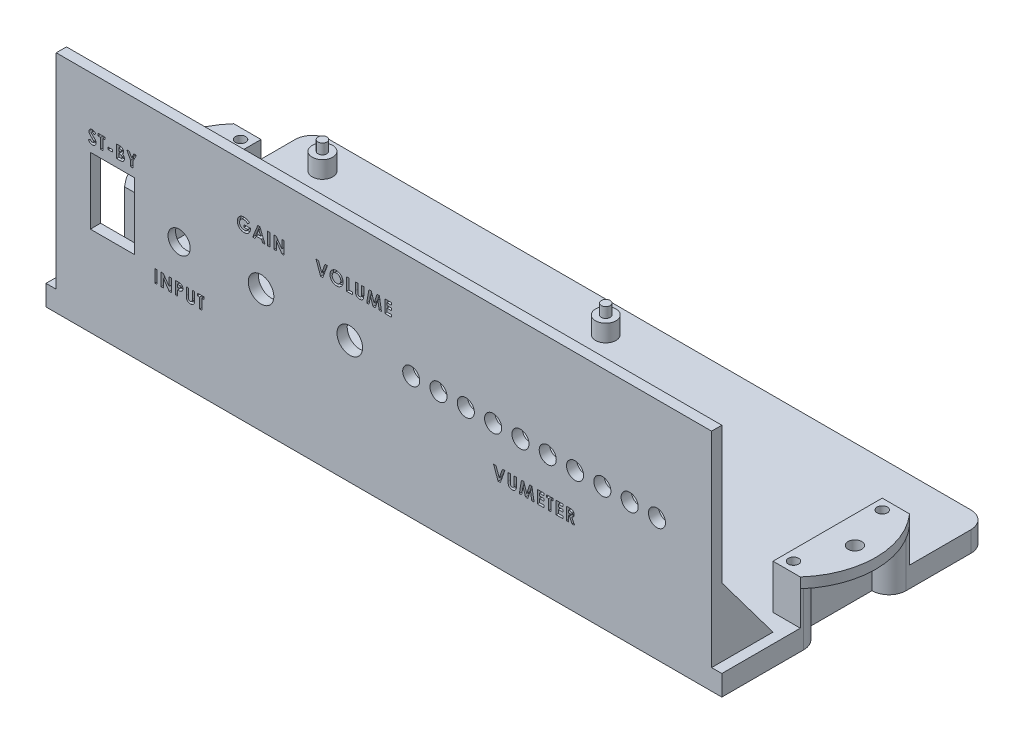
SolidWorks part; units mm, degrees
ref_plane "Alzado" through (0, 0, 0) normal (0, 0, 1) x (1, 0, 0)
ref_plane "Planta" through (0, 0, 0) normal (0, 1, 0) x (1, 0, 0)
ref_plane "Vista lateral" through (0, 0, 0) normal (1, 0, 0) x (0, 0, -1)
sketch "Croquis1" plane through (0, 0, 0) normal (0, 1, 0) x (1, 0, 0)
  line L0 (0, 39) -> (0, -39) construction
  line L1 (-99, 39) -> (99, 39)
  line L3 (-99, -39) -> (99, -39)
  line L10 (99, 39) -> (99, 10)
  line L11 (99, 10) -> (94, 10)
  line L12 (94, 10) -> (94, -10)
  line L13 (94, -10) -> (99, -10)
  line L14 (99, -10) -> (99, -39)
  line L15 (-99, 39) -> (-99, 10)
  line L16 (-99, 10) -> (-94, 10)
  line L17 (-94, 10) -> (-94, -10)
  line L18 (-94, -10) -> (-99, -10)
  line L19 (-99, -10) -> (-99, -39)
  line L20 (-94, 0) -> (4, 0) construction
  circle A0 centre (83, 5) radius 2
  circle A1 centre (6, 5) radius 2
  point P7 (0, 0)
  point P14 (-94, 0)
  point P16 (94, 0)
  dimension "D10" = 4
  dimension "D11" = 4
  dimension "D1" = 78
  dimension "D2" = 198
  dimension "D4" = 20
  dimension "D6" = 39
  dimension "D7" = 5
  dimension "D3" = 20
  dimension "D5" = 5
  dimension "D8" = 39
  dimension "D9" = 5
  dimension "D12" = 77
  dimension "14" = 11
  dimension "D14" = 44
extrude "Saliente-Extruir1" add sketch "Croquis1" along normal blind 6
sketch "Croquis18" plane through (0, 0, 0) normal (0, -1, 0) x (1, 0, 0)
  circle A0 centre (83, -5) radius 4
  circle A1 centre (6, -5) radius 4
  dimension "D1" = 8
  dimension "D2" = 8
extrude "Cortar-Extruir4" cut sketch "Croquis18" against normal blind 3
sketch "Croquis3" plane through (0, 6, 0) normal (0, 1, 0) x (1, 0, 0)
  line L17 (-99, 16) -> (-91, 16)
  line L18 (-99, 39) -> (-99, 10) construction
  line L19 (-91, 16) -> (-91, -16)
  line L20 (-91, -16) -> (-99, -16)
  line L21 (-99, -10) -> (-99, -39) construction
  line L22 (-99, -16) -> (-99, -10)
  line L23 (-99, -10) -> (-94, -10)
  line L24 (-94, -10) -> (-94, 10)
  line L25 (-94, 10) -> (-99, 10)
  line L26 (-99, 10) -> (-99, 16)
  line L27 (91, -16) -> (99, -16)
  line L28 (99, -39) -> (99, -10) construction
  line L29 (99, -16) -> (99, -10)
  line L30 (99, -10) -> (94, -10)
  line L31 (94, -10) -> (94, 10)
  line L32 (94, 10) -> (99, 10)
  line L33 (99, 10) -> (99, 16)
  line L34 (99, 10) -> (99, 39) construction
  line L35 (99, 16) -> (91, 16)
  line L36 (91, 16) -> (91, -16)
  point P26 (95, -16)
  line M5 (-99, 39) -> (-99, 10)
  line M13 (99, -39) -> (99, -10)
  line M14 (99, -10) -> (94, -10)
  line M16 (-99, 10) -> (-94, 10)
  line M17 (-94, 10) -> (-94, -10)
  line M18 (-94, -10) -> (-99, -10)
  line M19 (-99, -10) -> (-99, -39)
  line M20 (94, -10) -> (94, 10)
  line M21 (94, 10) -> (99, 10)
  line M22 (99, 10) -> (99, 39)
  dimension "D1" = 6
  dimension "D3" = 3
  dimension "D4" = 3
  dimension "D7" = 6
  dimension "D2" = 6
extrude "Saliente-Extruir2" add sketch "Croquis3" along normal blind 10 contours L20 L19 L17 M5 M16 M17 M18 M19 | L35 L36 L27 M13 M14 M20 M21 M22 region at (-95, 6, -15.6702) region at (91.3298, 6, 0)
sketch "Croquis5" plane through (0, 6, 0) normal (0, 1, 0) x (1, 0, 0)
  line L0 (-99, -39) -> (99, -39) construction
  line L1 (-96, -36) -> (96, -36)
  line L2 (-96, -36) -> (-96, -39)
  line L3 (-96, -39) -> (96, -39)
  line L4 (96, -36) -> (96, -39)
  point P4 (0, -39)
  point P7 (0, -39)
  dimension "D1" = 192
  dimension "D2" = 3
extrude "Saliente-Extruir3" add sketch "Croquis5" along normal blind 60
sketch "Croquis6" plane through (0, 16, 0) normal (0, 1, 0) x (1, 0, 0)
  line L0 (-99, -16) -> (-91, -16)
  line L1 (-91, -16) -> (-91, 16)
  line L2 (-91, 16) -> (-99, 16)
  line L3 (99, -16) -> (91, -16)
  line L4 (91, -16) -> (91, 16)
  line L5 (91, 16) -> (99, 16)
  arc A0 (-99, -16) -> (-99, 16) centre (-81.1115, 0) cw
  arc A1 (99, -16) -> (99, 16) centre (81.1115, 0) ccw
  dimension "D1" = 24
  dimension "D2" = 24
extrude "Saliente-Extruir4" add sketch "Croquis6" along normal blind 3
sketch "Croquis8" plane through (96, 0, 0) normal (1, 0, 0) x (0, 0, -1)
  line L0 (-36, 26) -> (-21, 6)
  line L1 (-36, 66) -> (-36, 6) construction
  line L2 (7, 6) -> (3, 6) construction
  dimension "D1" = 20
  dimension "D2" = 15
rib "Nervio1" sketch "Croquis8" sketch "Croquis8" thickness 3 extrusion direction parallel to sketch draft on no parameters "D1"=3
sketch "Croquis12" plane through (0, 6, 0) normal (0, 1, 0) x (1, 0, 0)
  line L0 (0, -39) -> (0, 39) construction
  line L1 (-96, -39) -> (96, -39) construction
  line L2 (99, 39) -> (-99, 39) construction
ref_plane "Plano1" through (0, 0, 0) normal (1, 0, 0) x (0, 0, -1)
mirror "Simetría1" about plane through (0, 0, 0) normal (1, 0, 0) of "Nervio1"
sketch "Croquis13" plane through (0, 6, 0) normal (0, 1, 0) x (1, 0, 0)
  line L0 (-99, 39) -> (-99, 16) construction
  line L1 (-87, -28) -> (-87, 30) construction
  line L4 (99, 39) -> (-99, 39) construction
  circle A0 centre (-87, -28) radius 3
  circle A1 centre (-87, 30) radius 3
  circle A2 centre (-4, 30) radius 3
  circle A3 centre (-4, -28) radius 3
  dimension "D7" = 6
  dimension "D6" = 6
  dimension "D3" = 6
  dimension "D4" = 6
  dimension "D1" = 58
  dimension "D2" = 12
  dimension "D5" = 83
  dimension "D8" = 9
extrude "Saliente-Extruir5" add sketch "Croquis13" along normal blind 5
sketch "Croquis14" plane through (0, 11, 0) normal (0, 1, 0) x (1, 0, 0)
  circle A0 centre (-87, 30) radius 1.3
  circle A1 centre (-87, -28) radius 1.3
  circle A2 centre (-87, -28) radius 3 construction
  circle A3 centre (-87, 30) radius 3 construction
  circle A4 centre (-4, 30) radius 1.3
  circle A5 centre (-4, -28) radius 1.3
  dimension "D1" = 2.6
  dimension "D2" = 2.6
  dimension "D3" = 2.6
  dimension "D4" = 2.6
extrude "Saliente-Extruir6" add sketch "Croquis14" along normal blind 3
sketch "Croquis15" plane through (0, 19, 0) normal (0, 1, 0) x (1, 0, 0)
  line L0 (-91, -16) -> (-91, 16) construction
  line L1 (91, 16) -> (91, -16) construction
  circle A0 centre (-99, 0) radius 2
  circle A1 centre (99, 0) radius 2
  point P7 (-91, 0)
  point P11 (91, 0)
  dimension "D1" = 4
  dimension "D3" = 4
  dimension "D2" = 8
  dimension "D4" = 8
extrude "Cortar-Extruir1" cut sketch "Croquis15" against normal up to surface (3 mm away) up to face at (98.3519, 16, 0)
fillet "Redondeo1" radius 5 6 edges at (-99, 8, 10) (-99, 8, -10) (-99, 3, -39) (99, 3, -39) (99, 8, 10) (99, 8, -10)
sketch "Croquis16" plane through (0, 19, 0) normal (0, 1, 0) x (1, 0, 0)
  line L0 (-91, 16) -> (-99, 16) construction
  line L1 (-91, -16) -> (-91, 16) construction
  line L2 (-99, -16) -> (-91, -16) construction
  line L3 (91, 16) -> (91, -16) construction
  line L4 (99, 16) -> (91, 16) construction
  line L5 (91, -16) -> (99, -16) construction
  circle A0 centre (94, 13) radius 1.5
  circle A1 centre (94, -13) radius 1.5
  circle A2 centre (-94, 13) radius 1.5
  circle A3 centre (-94, -13) radius 1.5
  dimension "D3" = 3
  dimension "D4" = 3
  dimension "D2" = 3
  dimension "D1" = 3
  dimension "D6" = 3
  dimension "D9" = 3
  dimension "D10" = 3
  dimension "D5" = 3
  dimension "D7" = 3
  dimension "D8" = 3
  dimension "D11" = 3
  dimension "D12" = 3
extrude "Cortar-Extruir2" cut sketch "Croquis16" against normal blind 3
fillet "Redondeo2" radius 1 4 edges at (-94, 16, 14.5) (-94, 16, -11.5) (94, 16, 14.5) (94, 16, -11.5)
sketch "Croquis17" plane through (0, 0, 39) normal (0, 0, 1) x (1, 0, 0)
  line L0 (-96, 66) -> (96, 66) construction
  line L1 (-86, 45.75) -> (-73, 45.75)
  line L2 (96, 66) -> (96, 6) construction
  line L4 (-86, 45.75) -> (-86, 26.25)
  line L5 (-86, 26.25) -> (-73, 26.25)
  line L6 (-73, 45.75) -> (-73, 26.25)
  line L7 (-96, 66) -> (-96, 6) construction
  line L8 (-20, 36) -> (0, 36) construction
  line L9 (-46, 36) -> (-26, 36) construction
  line L10 (-87, 36) -> (-72, 36) construction
  line L11 (-79.5, 45.75) -> (-79.5, 26.25) construction
  circle A0 centre (8, 36) radius 2.5
  circle A10 centre (16, 36) radius 2.5
  circle A11 centre (24, 36) radius 2.5
  circle A12 centre (32, 36) radius 2.5
  circle A13 centre (40, 36) radius 2.5
  circle A14 centre (48, 36) radius 2.5
  circle A15 centre (56, 36) radius 2.5
  circle A16 centre (64, 36) radius 2.5
  circle A17 centre (72, 36) radius 2.5
  circle A18 centre (80, 36) radius 2.5
  circle A19 centre (-10, 36) radius 3.75
  circle A20 centre (-36, 36) radius 3.75
  circle A21 centre (-60, 36) radius 3.25
  point P36 (-10, 36)
  point P41 (-36, 36)
  point P42 (-86, 36)
  point P47 (-79.5, 36)
  point P48 (-79.5, 36)
  dimension "D5" = 5
  dimension "D10" = 7.5
  dimension "D13" = 7.5
  dimension "D18" = 6.5
  dimension "D2" = 16
  dimension "D6" = 8
  dimension "D1" = 19.5
  dimension "D7" = 13
  dimension "D9" = 10
  dimension "D11" = 30
  dimension "D12" = 20
  dimension "D14" = 20
  dimension "D16" = 30
  dimension "D8" = 30
  dimension "D19" = 30
  dimension "D20" = 13
  dimension "D3" = 30
  dimension "D21" = 15
  dimension "D17" = 24
  dimension "D15" = 26
  dimension "D4" = 10
extrude "Cortar-Extruir3" cut sketch "Croquis17" against normal up to surface (3 mm away) up to face at (0, 31, 36)
sketch "Croquis21" plane through (0, 0, 39) normal (0, 0, 1) x (1, 0, 0)
  line L0 (-46, 48) -> (-26, 48) construction
  line L1 (-13.75, 36) -> (-6.25, 36) construction
  line L2 (-39.75, 36) -> (-32.25, 36) construction
  line L3 (-20, 48) -> (0, 48) construction
  line L4 (-89.5, 48) -> (-69.5, 48) construction
  line L5 (-73, 45.75) -> (-86, 45.75) construction
  line L6 (32, 22) -> (56, 22) construction
  line L7 (42.5, 36) -> (45.5, 36) construction
  line L8 (-63.25, 36) -> (-56.75, 36) construction
  line L9 (-70, 22) -> (-50, 22) construction
  circle A0 centre (-10, 36) radius 3.75 construction
  circle A1 centre (-36, 36) radius 3.75 construction
  circle A2 centre (40, 36) radius 2.5 construction
  circle A3 centre (48, 36) radius 2.5 construction
  circle A4 centre (-60, 36) radius 3.25 construction
  text T0 "GAIN" font "Century Gothic" height in points 14
  text T1 "VOLUME" font "Century Gothic" height in points 14
  text T2 "ST-BY" font "Century Gothic" height in points 14
  text T3 "VUMETER" font "Century Gothic" height in points 14
  text T4 "INPUT" font "Century Gothic" height in points 14
  point P2 (-36, 48)
  point P3 (-36, 36)
  point P17 (-10, 48)
  point P18 (-10, 36)
  point P22 (-79.5, 48)
  point P25 (-79.5, 45.75)
  point P35 (44, 36)
  point P36 (44, 22)
  point P45 (-60, 22)
  point P46 (-60, 36)
  dimension "D1" = 12
  dimension "D2" = 0
  dimension "D3" = 20
  dimension "D4" = 20
  dimension "D5" = 20
  dimension "D6" = 24
  dimension "14" = 14
  dimension "D8" = 20
  dimension "D9" = 14
extrude "Cortar-Extruir6" cut sketch "Croquis21" against normal blind 1
sketch "Croquis22" plane through (0, 0, 36) normal (0, 0, -1) x (-1, 0, 0)
  line L0 (55, 41.5) -> (65, 30.5) construction
  line L1 (55, 41.5) -> (65, 41.5)
  line L2 (55, 41.5) -> (55, 30.5)
  line L3 (55, 30.5) -> (65, 30.5)
  line L4 (65, 41.5) -> (65, 30.5)
  circle A0 centre (60, 36) radius 3.25 construction
  point P6 (60, 36)
  dimension "D1" = 10
  dimension "D2" = 11
extrude "Cortar-Extruir7" cut sketch "Croquis22" against normal blind 0.8
sketch "Croquis23" plane through (0, 0, 36) normal (0, 0, -1) x (-1, 0, 0)
  line L0 (6.25, 36) -> (2.25, 36) construction
  line L1 (27.25, 37.5) -> (28.25, 37.5)
  line L2 (27.25, 37.5) -> (27.25, 34.5)
  line L3 (27.25, 34.5) -> (28.25, 34.5)
  line L4 (28.25, 37.5) -> (28.25, 34.5)
  line L5 (1.25, 37.5) -> (2.25, 37.5)
  line L6 (1.25, 37.5) -> (1.25, 34.5)
  line L7 (1.25, 34.5) -> (2.25, 34.5)
  line L8 (2.25, 37.5) -> (2.25, 34.5)
  line L9 (32.25, 36) -> (28.25, 36) construction
  circle A0 centre (36, 36) radius 3.75 construction
  circle A2 centre (10, 36) radius 3.75 construction
  point P11 (2.25, 36)
  point P17 (28.25, 36)
  dimension "D1" = 3
  dimension "D2" = 1
  dimension "D3" = 4
  dimension "D4" = 1
  dimension "D5" = 3
  dimension "D6" = 4
extrude "Cortar-Extruir8" cut sketch "Croquis23" against normal blind 2
equation "\"grosor\"= 3"
equation "\"D1@Saliente-Extruir1\"= 2 * \"grosor\""
equation "\"D4@Croquis3\"=\"grosor\""
equation "\"D3@Croquis3\"=\"grosor\""
equation "\"D2@Croquis5\"=\"grosor\""
equation "\"largo_externo\"=198"
equation "\"D2@Croquis1\"=\"largo_externo\""
equation "\"ancho_externo\"=78"
equation "\"D1@Croquis1\"=\"ancho_externo\""
equation "\"D6@Croquis1\"=\"ancho_externo\" / 2"
equation "\"D8@Croquis1\"=\"ancho_externo\" / 2"
equation "\"D1@Croquis5\"=\"largo_externo\" - (2 * \"grosor\")"
equation "\"D8@Croquis13\"=6 +\"grosor\""
equation "\"D1@Saliente-Extruir4\"=\"grosor\""
equation "\"D7@Croquis3\"= 2 * \"grosor\""
equation "\"D1@Croquis3\"= 2 * \"grosor\""
equation "\"D2@Croquis3\"=2 * \"grosor\""
equation "\"D1@Croquis16\"=\"grosor\""
equation "\"D2@Croquis16\"=\"grosor\""
equation "\"D3@Croquis16\"=\"grosor\""
equation "\"D4@Croquis16\"=\"grosor\""
equation "\"D5@Croquis16\"=\"grosor\""
equation "\"D6@Croquis16\"=\"grosor\""
equation "\"D7@Croquis16\"=\"grosor\""
equation "\"D8@Croquis16\"=\"grosor\""
equation "\"D9@Croquis16\"=\"grosor\""
equation "\"D10@Croquis16\"=\"grosor\""
equation "\"D12@Croquis16\"=\"grosor\""
equation "\"D1@Cortar-Extruir2\"=\"grosor\""
equation "\"D14@Croquis1\"=\"ancho_externo\" / 2 + 5"
equation "\"D1@Cortar-Extruir4\"=\"grosor\""
equation "\"altura_interna\"= 60"
equation "\"D1@Saliente-Extruir3\"=\"altura_interna\""
equation "\"D8@Croquis17\"=\"altura_interna\"/2"
equation "\"D16@Croquis17\"=\"altura_interna\"/2"
equation "\"D11@Croquis17\"=\"altura_interna\"/2"
equation "\"D19@Croquis17\"=\"altura_interna\"/2"
equation "\"D3@Croquis17\"=\"altura_interna\"/2"
